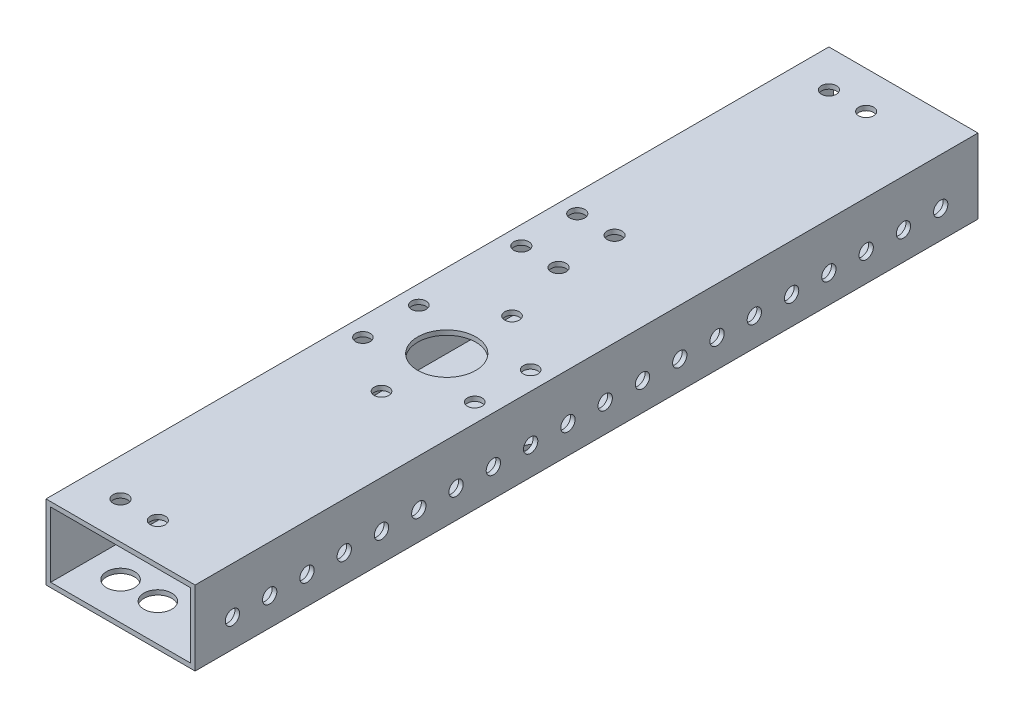
SolidWorks part; units mm, degrees
other "Markup1"
sketch "Sketch7" plane through (25.4, 12.7, -127) normal (0.9965, 0.0171, -0.0817) x (-0.082, 0.0128, -0.9966)
sketch "Sketch8" plane through (25.4, 12.7, -127) normal (0.9965, 0.0171, -0.0817) x (-0.082, 0.0128, -0.9966)
sketch "Sketch9" plane through (25.4, 12.7, -127) normal (0.9965, 0.0171, -0.0817) x (-0.082, 0.0128, -0.9966)
sketch "Sketch12" plane through (25.4, 12.7, -127) normal (0.9965, 0.0171, -0.0817) x (-0.082, 0.0128, -0.9966)
sketch "Sketch13" plane through (25.4, 12.7, -127) normal (0.9965, 0.0171, -0.0817) x (-0.082, 0.0128, -0.9966)
sketch "Sketch14" plane through (25.4, 12.7, -127) normal (0.9965, 0.0171, -0.0817) x (-0.082, 0.0128, -0.9966)
material "6061-T6 (SS)"
ref_plane "Front Plane" through (0, 0, 0) normal (0, 0, 1) x (1, 0, 0)
ref_plane "Top Plane" through (0, 0, 0) normal (0, 1, 0) x (1, 0, 0)
ref_plane "Right Plane" through (0, 0, 0) normal (1, 0, 0) x (0, 0, -1)
sketch "Sketch1" plane through (0, 0, 0) normal (0, 0, 1) x (1, 0, 0)
  line L0 (-23.8125, 11.1125) -> (23.8125, 11.1125)
  line L1 (-25.4, -12.7) -> (25.4, -12.7)
  line L2 (-25.4, -12.7) -> (-25.4, 12.7)
  line L3 (-25.4, 12.7) -> (25.4, 12.7)
  line L4 (25.4, -12.7) -> (25.4, 12.7)
  line L5 (-25.4, -12.7) -> (25.4, 12.7) construction
  line L6 (-25.4, 12.7) -> (25.4, -12.7) construction
  line L7 (23.8125, -11.1125) -> (23.8125, 11.1125)
  line L8 (-23.8125, -11.1125) -> (23.8125, -11.1125)
  line L9 (-23.8125, -11.1125) -> (-23.8125, 11.1125)
  point P0 (0, 0)
  dimension "D1" = 50.8
  dimension "D2" = 25.4
  dimension "D3" = 1.5875
extrude "Boss-Extrude1" add sketch "Sketch1" along normal mid plane 266.7
sketch "Sketch3" plane through (0, 12.7, 0) normal (0, 1, 0) x (1, 0, 0)
  line L0 (25.4, 133.35) -> (-25.4, 133.35) construction
  line L1 (25.4, -133.35) -> (-25.4, -133.35) construction
  line L3 (-25.4, -133.35) -> (-25.4, 133.35) construction
  line L4 (25.4, -133.35) -> (25.4, 133.35) construction
  circle A0 centre (-12.7, -120.65) radius 2.5527
  circle A1 centre (0, -120.65) radius 2.5527
  circle A2 centre (-12.7, 120.65) radius 2.5527
  circle A3 centre (0, 120.65) radius 2.5527
  dimension "D5" = 5.1054
  dimension "D1" = 12.7
  dimension "D2" = 12.7
  dimension "D3" = 12.7
  dimension "D4" = 12.7
  dimension "D6" = 12.7
  dimension "D7" = 12.7
  dimension "D8" = 12.7
  dimension "D9" = 25.4
  dimension "D10" = 12.7
  dimension "D11" = 25.4
extrude "Cut-Extrude1" cut sketch "Sketch3" against normal up to surface (1.5875 mm away) up to face at (0, 11.1125, 0)
sketch "Sketch5" plane through (0, -12.7, 0) normal (0, -1, 0) x (1, 0, 0)
  circle A0 centre (-12.7, -120.65) radius 2.5527 construction
  circle A1 centre (0, -120.65) radius 2.5527 construction
  circle A2 centre (0, 120.65) radius 2.5527 construction
  circle A3 centre (-12.7, 120.65) radius 2.5527 construction
  circle A4 centre (-12.7, -120.65) radius 2.5527
  circle A5 centre (0, -120.65) radius 2.5527
  circle A6 centre (0, 120.65) radius 2.5527
  circle A7 centre (-12.7, 120.65) radius 2.5527
  circle A8 centre (-12.7, 120.65) radius 4.7625
  circle A9 centre (0, 120.65) radius 4.7625
  circle A10 centre (0, -120.65) radius 4.7625
  circle A11 centre (-12.7, -120.65) radius 4.7625
  dimension "D1" = 9.525
extrude "Cut-Extrude2" cut sketch "Sketch5" against normal up to surface (1.5875 mm away) contours A10 A5 | A5 | A11 A4 | A4 | A6 | A9 A6 | A8 A7 | A7 region at (-12.7, -12.7, -120.65) region at (0, -12.7, -120.65) region at (0, -12.7, 120.65) region at (-12.7, -12.7, 120.65) region at (-17.3278, -12.7, 120.65) region at (-4.6278, -12.7, 120.65) region at (-4.6278, -12.7, -120.65) region at (-17.3278, -12.7, -120.65) up to face at (0, -11.1125, 0)
sketch "Sketch6" plane through (25.4, 0, 0) normal (1, 0, 0) x (0, 0, -1)
  line L0 (-133.35, -12.7) -> (-133.35, 12.7) construction
  line L1 (-133.35, -12.7) -> (133.35, -12.7) construction
  line L2 (0, 12.7) -> (0, -12.7) construction
  line L3 (-133.35, 12.7) -> (133.35, 12.7) construction
  circle A0 centre (-120.65, -3.175) radius 2.4384
  circle A19 centre (-107.95, -3.175) radius 2.4384
  circle A20 centre (-95.25, -3.175) radius 2.4384
  circle A21 centre (-82.55, -3.175) radius 2.4384
  circle A22 centre (-69.85, -3.175) radius 2.4384
  circle A23 centre (-57.15, -3.175) radius 2.4384
  circle A24 centre (-44.45, -3.175) radius 2.4384
  circle A25 centre (-31.75, -3.175) radius 2.4384
  circle A26 centre (-19.05, -3.175) radius 2.4384
  circle A27 centre (-6.35, -3.175) radius 2.4384
  circle A28 centre (6.35, -3.175) radius 2.4384
  circle A29 centre (19.05, -3.175) radius 2.4384
  circle A30 centre (31.75, -3.175) radius 2.4384
  circle A31 centre (44.45, -3.175) radius 2.4384
  circle A32 centre (57.15, -3.175) radius 2.4384
  circle A33 centre (69.85, -3.175) radius 2.4384
  circle A34 centre (82.55, -3.175) radius 2.4384
  circle A35 centre (95.25, -3.175) radius 2.4384
  circle A36 centre (107.95, -3.175) radius 2.4384
  circle A37 centre (120.65, -3.175) radius 2.4384
  point P2 (0, 0)
  point P3 (0, 0)
  dimension "D1" = 4.8768
  dimension "D5" = 12.7
  dimension "D2" = 12.7
  dimension "D3" = 9.525
  dimension "D4" = 20
extrude "Cut-Extrude3" cut sketch "Sketch6" against normal up to next contours A0 | A19 | A20 | A21 | A23 | A22 | A24 | A25 | A26 | A27 | A28 | A29 | A30 | A31 | A32 | A37 | A36 | A35 | A34 | A33 | A24 | A33 region at (25.4, -3.175, 120.65) region at (25.4, -3.175, 107.95) region at (25.4, -3.175, 95.25) region at (25.4, -3.175, 82.55) region at (25.4, -3.175, 69.85) region at (25.4, -3.175, 57.15) region at (25.4, -3.175, 44.45) region at (25.4, -3.175, 31.75) region at (25.4, -3.175, 19.05) region at (25.4, -3.175, 6.35) region at (25.4, -3.175, -6.35) region at (25.4, -3.175, -19.05) region at (25.4, -3.175, -31.75) region at (25.4, -3.175, -44.45) region at (25.4, -3.175, -57.15) region at (25.4, -3.175, -69.85) region at (25.4, -3.175, -82.55) region at (25.4, -3.175, -95.25) region at (25.4, -3.175, -107.95) region at (25.4, -3.175, -120.65)
sketch "Sketch11" plane through (0, 12.7, 0) normal (0, 1, 0) x (1, 0, 0)
  line L0 (-25.4, -133.35) -> (-25.4, 133.35) construction
  line L1 (-6.35, 41.275) -> (-6.35, 22.225) construction
  line L2 (0, 0) -> (0, -44.45) construction
  line L3 (25.4, 133.35) -> (-25.4, 133.35) construction
  line L4 (19.05, -31.75) -> (-19.05, -31.75) construction
  line L5 (-19.05, 41.275) -> (-3.7973, 41.275) construction
  line L6 (-19.05, 41.275) -> (-19.05, 22.225) construction
  line L7 (-19.05, 22.225) -> (-3.7973, 22.225) construction
  line L9 (-19.05, 41.275) -> (-16.8611, 39.9616) construction
  line L10 (-19.05, 22.225) -> (-16.8611, 23.5384) construction
  line L11 (19.05, -31.75) -> (19.05, -12.7) construction
  line L12 (19.05, -12.7) -> (-19.05, -12.7) construction
  line L13 (-19.05, -31.75) -> (-19.05, -12.7) construction
  line L14 (19.05, -31.75) -> (-19.05, -12.7) construction
  line L15 (19.05, -12.7) -> (-19.05, -31.75) construction
  circle A0 centre (0, -22.225) radius 9.906
  circle A1 centre (0, 0) radius 2.4892
  circle A2 centre (0, -44.45) radius 2.4892
  circle A4 centre (-19.05, 22.225) radius 2.5527
  circle A5 centre (-19.05, 41.275) radius 2.5527
  circle A7 centre (-6.35, 22.225) radius 2.5527
  circle A8 centre (-6.35, 41.275) radius 2.5527
  circle A9 centre (-19.05, -31.75) radius 2.4892
  circle A10 centre (-19.05, -12.7) radius 2.4892
  circle A11 centre (19.05, -12.7) radius 2.4892
  circle A12 centre (19.05, -31.75) radius 2.4892
  point P2 (0, -22.225)
  point P8 (-3.175, 31.75)
  point P9 (0, 0)
  point P16 (-3.175, 31.75)
  point P19 (0, 0)
  point P35 (0, 0)
  point P36 (0, 0)
  point P37 (0, 0)
  dimension "D1" = 19.812
  dimension "D3" = 4.9784
  dimension "D4" = 22.225
  dimension "D5" = 19.05
  dimension "D6" = 5.1054
  dimension "D7" = 12.7
  dimension "D10" = 19.05
  dimension "D2" = 22.225
  dimension "D8" = 101.6
  dimension "D9" = 6.35
  dimension "D11" = 19.05
  dimension "D12" = 22.225
extrude "Cut-Extrude4" cut sketch "Sketch11" against normal through all
